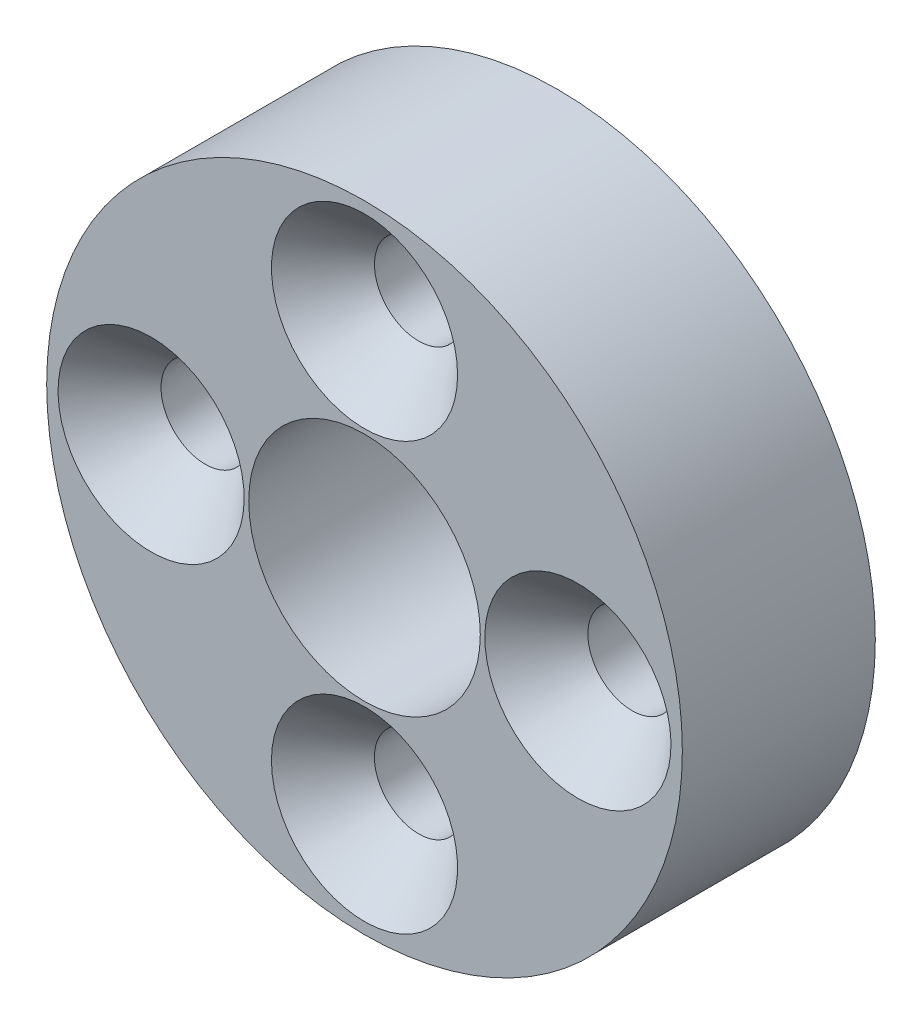
SolidWorks part; units mm, degrees
material "1060 Alloy"
ref_plane "Front Plane" through (0, 0, 0) normal (0, 0, 1) x (1, 0, 0)
ref_plane "Top Plane" through (0, 0, 0) normal (0, 1, 0) x (1, 0, 0)
ref_plane "Right Plane" through (0, 0, 0) normal (1, 0, 0) x (0, 0, -1)
sketch "Sketch1" plane through (0, 0, 0) normal (0, 0, 1) x (1, 0, 0)
  line L0 (0, 11.938) -> (0, 0) construction
  line L5 (0, 0) -> (11.938, 0) construction
  line L6 (0, -11.938) -> (0, 0) construction
  line L7 (0, 0) -> (-11.938, 0) construction
  circle A0 centre (0, 0) radius 17.78
  circle A1 centre (-11.938, 0) radius 2.4765
  circle A2 centre (0, -11.938) radius 2.4765
  circle A3 centre (11.938, 0) radius 2.4765
  circle A4 centre (0, 11.938) radius 2.4765
  circle A5 centre (0, 0) radius 6.477
  dimension "D1" = 35.56
  dimension "D4" = 4.953
  dimension "D2" = 12.954
  dimension "D3" = 11.938
extrude "Boss-Extrude1" add sketch "Sketch1" along normal blind 10.795
sketch "Sketch2" plane through (0, 0, 0) normal (0, 0, -1) x (-1, 0, 0)
  line L1 (-8.255, -8.255) -> (8.255, -8.255)
  line L2 (-8.255, -8.255) -> (-8.255, 8.255)
  line L3 (-8.255, 8.255) -> (8.255, 8.255)
  line L4 (8.255, -8.255) -> (8.255, 8.255)
  line L5 (-8.255, -8.255) -> (8.255, 8.255) construction
  line L6 (-8.255, 8.255) -> (8.255, -8.255) construction
  circle A0 centre (0, 0) radius 6.477 construction
  circle A1 centre (0, 0) radius 6.477
  point P0 (0, 0)
  dimension "D1" = 16.51
extrude "Boss-Extrude2" add sketch "Sketch2" along normal blind 3.175
sketch "Sketch5" plane through (0, 0, 0) normal (1, 0, 0) x (0, 0, -1)
  line L0 (-10.795, 11.938) -> (0, 11.938) construction
  line L1 (-10.795, 14.4145) -> (-10.795, 9.4615) construction
  line L2 (0, 9.4615) -> (0, 14.4145) construction
  line L3 (-10.795, 11.938) -> (-10.795, 17.145)
  line L4 (-10.795, 17.78) -> (-10.795, -17.78) construction
  line L5 (-10.795, 17.145) -> (-7.493, 14.1719)
  line L6 (-7.493, 14.1719) -> (-7.493, 11.938)
  line L7 (-7.493, 11.938) -> (-10.795, 11.938)
  dimension "D1" = 42
  dimension "D2" = 5.207
  dimension "D3" = 3.302
revolve "Cut-Revolve1" cut sketch "Sketch5" angle 360 about L0
pattern_circular "CirPattern4" count 4 over 360 about axis through (0, 0, 10.795) along (0, 0, 1) of "Cut-Revolve1"
